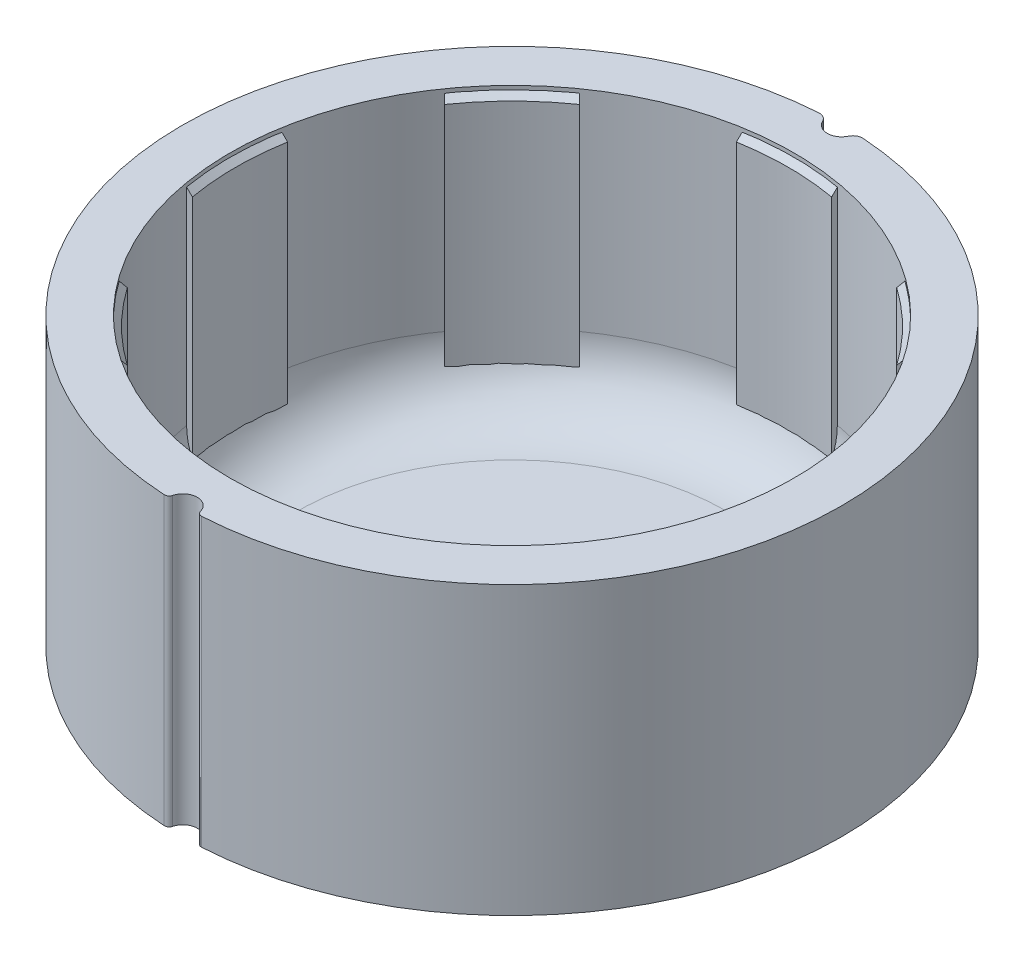
SolidWorks part; units mm, degrees
other "Markup1"
sketch "Sketch4"
other "Markup5"
sketch "Sketch8" plane through (34.5, 25, 34.4428) normal (0.0041, 0.9851, 0.1719) x (0.981, -0.0374, 0.1906)
other "Markup6"
sketch "Sketch9" plane through (34.5, 25, 34.4428) normal (0.0041, 0.9851, 0.1719) x (0.981, -0.0374, 0.1906)
other "Markup7"
sketch "Sketch10" plane through (-34.5, 25, 34.4428) normal (-0.125, 0.9874, 0.0969) x (0.5933, -0.0039, 0.805)
ref_plane "Front Plane" through (0, 0, 0) normal (0, 0, 1) x (1, 0, 0)
ref_plane "Top Plane" through (0, 0, 0) normal (0, 1, 0) x (1, 0, 0)
ref_plane "Right Plane" through (0, 0, 0) normal (1, 0, 0) x (0, 0, -1)
sketch "Sketch1" plane through (0, 0, 0) normal (0, 1, 0) x (1, 0, 0)
  line L3 (0, 0.002) -> (0, 3.7877) construction
  line L4 (0, 3.7877) -> (2.417, 3.7877)
  line L5 (0, 3.7877) -> (-2.417, 3.7877)
  arc A0 (1.9642, -34.442) -> (34.1982, 4.5552) centre (0, 0.002) ccw
  arc A2 (-2.417, 3.7877) -> (2.417, 3.7877) centre (0, 0.002) ccw
  circle A3 centre (0, 0.002) radius 34.5 construction
  arc A7 (-1.3541, 33.8562) -> (1.3541, 33.8562) centre (0, 34.5015) ccw
  arc A8 (34.1982, 4.5552) -> (2.3241, 34.4236) centre (0, 0.002) ccw
  arc A9 (-2.3241, 34.4236) -> (-34.1982, 4.5552) centre (0, 0.002) ccw
  arc A10 (-34.1982, 4.5552) -> (-1.9642, -34.442) centre (0, 0.002) ccw
  arc A11 (1.3541, 33.8562) -> (2.3241, 34.4236) centre (2.2568, 33.4259) cw
  arc A12 (-1.3541, 33.8562) -> (-2.3241, 34.4236) centre (-2.2568, 33.4259) ccw
  arc A13 (1.4518, -34.0686) -> (-1.4518, -34.0686) centre (0, -34.4457) ccw
  arc A14 (1.4518, -34.0686) -> (1.9642, -34.442) centre (1.9358, -33.9428) ccw
  arc A15 (-1.4518, -34.0686) -> (-1.9642, -34.442) centre (-1.9358, -33.9428) cw
  point P15 (1.4997, 34.4694)
  dimension "D2" = 4.834
  dimension "D3" = 4.4915
  dimension "D4" = 34.5
  dimension "D5" = 1
  dimension "D6" = 1.5
  dimension "D7" = 0.5
  dimension "D11" = 1.4997
sketch "Sketch2" plane through (0, 0, 0) normal (0, 1, 0) x (1, 0, 0)
  line L0 (0, 29.5) -> (0, 28.9) construction
  line L1 (-4.982, 29.0763) -> (0, 29.5) construction
  line L2 (0, 29.5) -> (4.982, 29.0763) construction
  line L3 (-4.982, 29.0763) -> (-4.982, 28.4673)
  line L6 (4.982, 28.4673) -> (4.982, 29.0763)
  circle A16 centre (0, 0) radius 29.5
  arc A18 (-4.982, 28.4673) -> (4.982, 28.4673) centre (0, 0) cw
  point P3 (0, 28.9)
  dimension "D1" = 59
  dimension "D2" = 5
  dimension "D3" = 0.6
extrude "Boss-Extrude1" add sketch "Sketch1" along normal blind 30 contours A10 A0 A8 A7 A9 A2 L5 L4 | L5 A2 L4 region at (0, 0, 0.1522) region at (2.2155, 0, 33.5591)
extrude "Cut-Extrude2" cut sketch "Sketch2" along normal up to next from offset 1 contours A16 | A16 region at (0, 0, 0.064)
extrude "Boss-Extrude2" add sketch "Sketch2<2>" along normal up to surface (30 mm away) separate body contours A16 region at (0, 0, -29.0571) up to face at (0, 30, 29.5)
sketch "Sketch2<2>" plane through (0, 0, 0) normal (0, 1, 0) x (1, 0, 0) same geometry as "Sketch2"
chamfer "Chamfer2" distance 1 angle 45 1 edges at (0, 30, -28.9)
pattern_circular "CirPattern2" count 8 over 360 about axis through (0, 30, 0) along (0, 1, 0) of bodies 106
fillet "Fillet2" radius 7 1 edges at (0, 1, 29.5)
